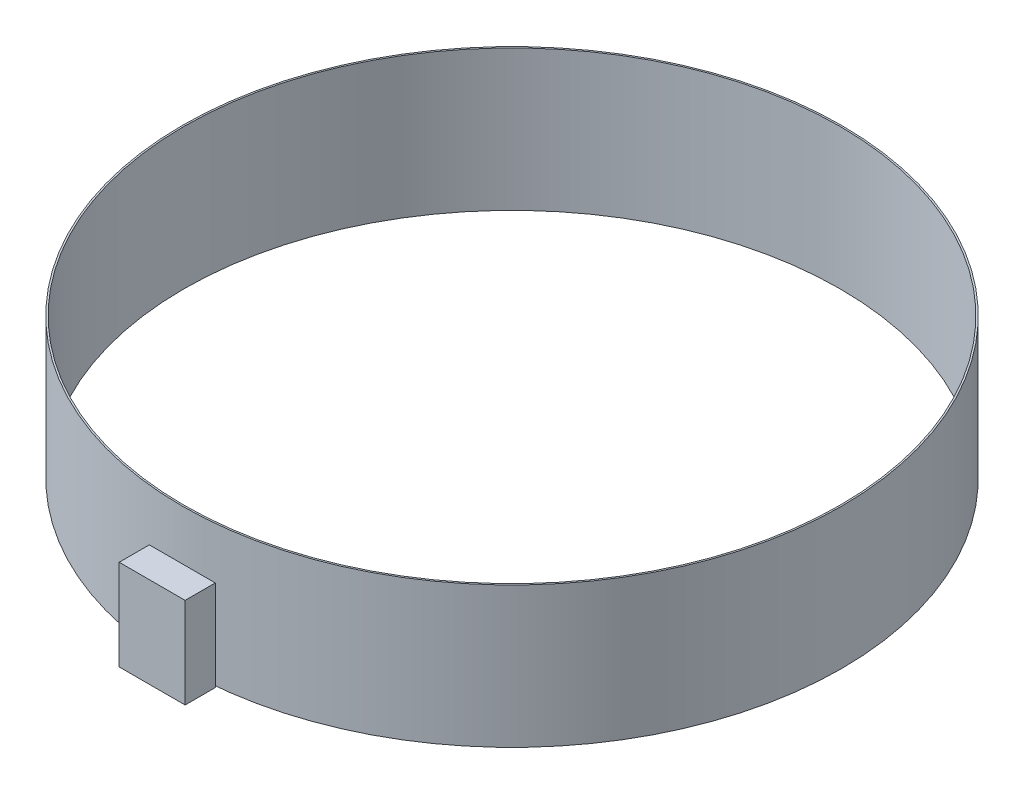
SolidWorks part; units mm, degrees
ref_plane "Front Plane" through (0, 0, 0) normal (0, 0, 1) x (1, 0, 0)
ref_plane "Top Plane" through (0, 0, 0) normal (0, 1, 0) x (1, 0, 0)
ref_plane "Right Plane" through (0, 0, 0) normal (1, 0, 0) x (0, 0, -1)
sketch "Sketch1" plane through (0, 0, 0) normal (0, 1, 0) x (1, 0, 0)
  circle A0 centre (0, 0) radius 10000
  circle A1 centre (0, 0) radius 9850
extrude "Boss-Extrude1" add sketch "Sketch1" along normal blind 4267.2 contours A0
sketch "Sketch2" plane through (0, 4267.2, 0) normal (0, 1, 0) x (1, 0, 0)
  circle A0 centre (0, 0) radius 9950
  circle A1 centre (0, 0) radius 10000 construction
  dimension "D1" = 50
extrude "Cut-Extrude1" cut sketch "Sketch2" against normal blind 4267.2 contours A0
ref_plane "Plane2" through (0, 0, 10000) normal (0, 0, 1) x (1, 0, 0)
sketch "Sketch4" plane through (0, 0, 10000) normal (0, 0, 1) x (1, 0, 0)
  line L0 (0, -2346.96) -> (0, 2346.96) construction
  line L1 (1000, 0) -> (-1000, 0)
  line L2 (1000, 0) -> (1000, 2750)
  line L3 (1000, 2750) -> (-1000, 2750)
  line L4 (-1000, 0) -> (-1000, 2750)
  line L5 (1000, 0) -> (-1000, 2750) construction
  line L6 (1000, 2750) -> (-1000, 0) construction
  line L7 (11000, 0) -> (-11000, 0) construction
  point P0 (0, 1375)
  dimension "D1" = 2750
  dimension "D2" = 2000
extrude "Boss-Extrude2" add sketch "Sketch4" along normal blind 914.4 separate body
